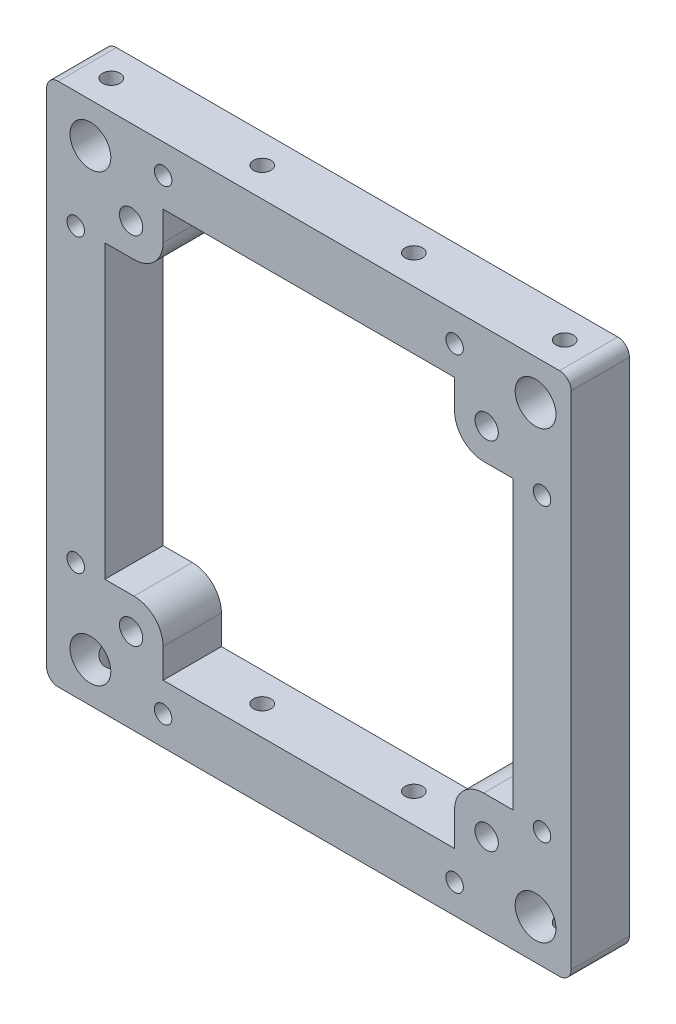
SolidWorks part; units mm, degrees
ref_plane "Front Plane" through (0, 0, 0) normal (0, 0, 1) x (1, 0, 0)
ref_plane "Top Plane" through (0, 0, 0) normal (0, 1, 0) x (1, 0, 0)
ref_plane "Right Plane" through (0, 0, 0) normal (1, 0, 0) x (0, 0, -1)
sketch "Sketch1" plane through (0, 0, 0) normal (0, 0, 1) x (1, 0, 0)
  line L0 (-45, 0.8199) -> (45, 0.8199) construction
  line L1 (45, -6) -> (-45, -6)
  line L2 (45, -6) -> (45, 7.6399)
  line L4 (-45, -6) -> (-45, 7.6399)
  line L5 (45, -6) -> (-6.1495, 0.8199) construction
  line L6 (45, 7.6399) -> (-45, -6) construction
  line L7 (0.7078, 14.0107) -> (0, -10937.857) construction
  line L8 (-50.4363, 39) -> (55.0192, 39) construction
  line L9 (45, 84) -> (45, 70.3601)
  line L10 (45, 84) -> (-45, 84)
  line L11 (-45, 84) -> (-45, 70.3601)
  line L13 (45, 70.3601) -> (45, 7.6399)
  line L14 (-45, 70.3601) -> (-45, 7.6399)
  line L17 (0, 84) -> (0, -10937.857) construction
  line L18 (-25, 74) -> (25, 74)
  line L19 (30.5, 8.5) -> (-30.5, 8.5) construction
  line L20 (30.5, 8.5) -> (30.5, 69.5) construction
  line L21 (30.5, 69.5) -> (-30.5, 69.5) construction
  line L22 (-30.5, 8.5) -> (-30.5, 69.5) construction
  line L23 (30.5, 8.5) -> (-30.5, 69.5) construction
  line L24 (30.5, 69.5) -> (-30.5, 8.5) construction
  line L25 (-25, 74) -> (-25, 64)
  line L26 (25, 74) -> (25, 64)
  line L27 (35, 64) -> (35, 14.7435)
  line L28 (35, 14.7435) -> (25, 14.7435)
  line L29 (35, 64) -> (25, 64)
  line L30 (-25, 4) -> (25, 4)
  line L31 (-25, 14) -> (-25, 4)
  line L32 (25, 14.7435) -> (25, 4)
  line L33 (-35, 64) -> (-35, 14)
  line L34 (-25, 14) -> (-35, 14)
  line L35 (-25, 64) -> (-35, 64)
  circle A0 centre (-37.4781, 0.8199) radius 3.5
  circle A1 centre (38.8919, 0.815) radius 3.5
  circle A2 centre (-37.4781, 77.1801) radius 3.5
  circle A3 centre (38.8919, 77.185) radius 3.5
  circle A5 centre (-30.5, 69.5) radius 2
  circle A6 centre (30.5, 69.5) radius 2
  circle A7 centre (30.5, 8.5) radius 2
  circle A8 centre (-30.5, 8.5) radius 2
  point P0 (0, 0)
  point P30 (-25, 9)
  dimension "D4" = 7
  dimension "D8" = 6
  dimension "D11" = 10
  dimension "D14" = 4
  dimension "D19" = 76.37
  dimension "D2" = 90
  dimension "D3" = 108
  dimension "D5" = 90
  dimension "D6" = 30.5
  dimension "D7" = 10
  dimension "D9" = 45
  dimension "D10" = 38.8919
  dimension "D12" = 61
  dimension "D13" = 61
  dimension "D15" = 10
  dimension "D16" = 10
  dimension "D17" = 20
  dimension "D18" = 20
  dimension "D20" = 76.37
extrude "Boss-Extrude1" add sketch "Sketch1" along normal blind 10
fillet "Fillet3" radius 2 4 edges at (-45, 84, 5) (45, 84, 5) (45, -6, 5) (-45, -6, 5)
sketch "Sketch3" plane through (0, -6, 0) normal (0, -1, 0) x (1, 0, 0)
  line L0 (-43, 5) -> (43, 5) construction
  line L1 (-43, 10) -> (-43, 0) construction
  line L2 (43, 0) -> (43, 10) construction
  line L3 (0, 0) -> (0, 10) construction
  line L4 (-43, 10) -> (43, 10) construction
  circle A0 centre (-13, 5) radius 1.5
  circle A1 centre (13, 5) radius 1.5
  dimension "D1" = 26
  dimension "D2" = 3
extrude "Cut-Extrude2" cut sketch "Sketch3" against normal blind 90
sketch "Sketch5" plane through (0, -6, 0) normal (0, -1, 0) x (1, 0, 0)
  line L0 (-43, 5) -> (43, 5) construction
  line L1 (-43, 10) -> (-43, 0) construction
  line L2 (43, 0) -> (43, 10) construction
  line L3 (0, 0) -> (0, 10) construction
  line L4 (-43, 0) -> (43, 0) construction
  line L5 (-43, 10) -> (43, 10) construction
  circle A0 centre (-38.89, 5) radius 1.5
  circle A1 centre (38.89, 5) radius 1.5
  dimension "D1" = 77.78
  dimension "D2" = 3
extrude "Cut-Extrude4" cut sketch "Sketch5" against normal up to next
sketch "Sketch6" plane through (0, 84, 0) normal (0, 1, 0) x (1, 0, 0)
  line L0 (-43, -5) -> (43, -5) construction
  line L1 (-43, 0) -> (-43, -10) construction
  line L2 (43, -10) -> (43, 0) construction
  line L3 (0, 0) -> (0, -10) construction
  line L5 (43, -10) -> (-43, -10) construction
  circle A0 centre (-38.89, -5) radius 1.5
  circle A1 centre (38.89, -5) radius 1.5
  dimension "D1" = 77.78
  dimension "D2" = 3
extrude "Cut-Extrude5" cut sketch "Sketch6" against normal up to next
fillet "Fillet5" radius 5 4 edges at (25, 14.7435, 5) (-25, 14, 5) (-25, 64, 5) (25, 64, 5)
sketch "Sketch7" plane through (0, 0, 10) normal (0, 0, 1) x (1, 0, 0)
  line L0 (0, 84) -> (0, -6) construction
  line L1 (43, 84) -> (-43, 84) construction
  line L2 (-43, -6) -> (43, -6) construction
  line L3 (-45, 39) -> (45, 39) construction
  line L4 (-45, 82) -> (-45, -4) construction
  line L5 (45, -4) -> (45, 82) construction
  line L6 (-30.3822, 79) -> (27.4035, 79) construction
  line L7 (38.8919, 77.185) -> (-37.4781, 0.8199) construction
  line L8 (40, 68.429) -> (40, 14.0985) construction
  circle A0 centre (-25, 79) radius 1.5
  circle A1 centre (25, 79) radius 1.5
  circle A2 centre (25, -1) radius 1.5
  circle A3 centre (-25, -1) radius 1.5
  circle A6 centre (40, 64) radius 1.5
  circle A7 centre (40, 14) radius 1.5
  circle A8 centre (-40, 14) radius 1.5
  circle A9 centre (-40, 64) radius 1.5
  dimension "D3" = 3
  dimension "D4" = 5
  dimension "D5" = 50
  dimension "D6" = 3
  dimension "D1" = 5
  dimension "D2" = 50
extrude "Cut-Extrude6" cut sketch "Sketch7" against normal up to next
